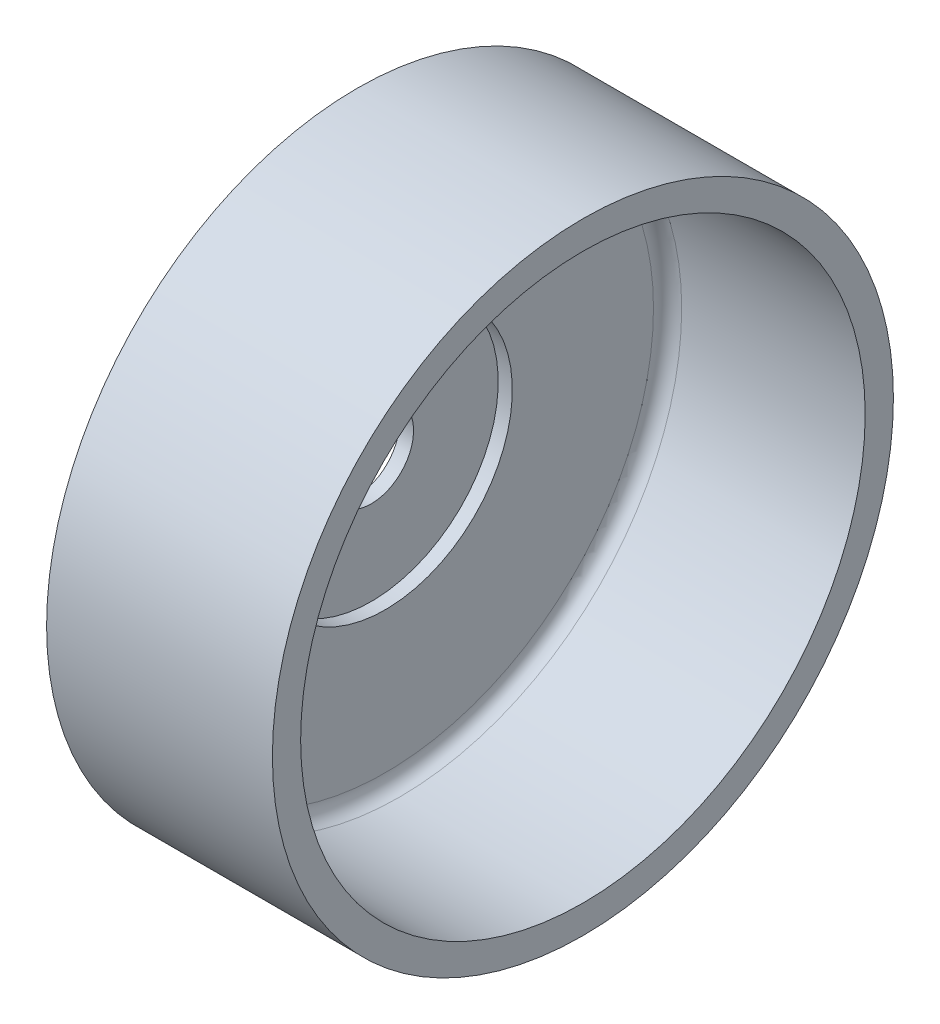
SolidWorks part; units mm, degrees
ref_plane "Front Plane" through (0, 0, 0) normal (0, 0, 1) x (1, 0, 0)
ref_plane "Top Plane" through (0, 0, 0) normal (0, 1, 0) x (1, 0, 0)
ref_plane "Right Plane" through (0, 0, 0) normal (1, 0, 0) x (0, 0, -1)
sketch "Sketch1" plane through (0, 0, 0) normal (0, 1, 0) x (1, 0, 0)
  line L0 (0, 4.7625) -> (0, 34.925)
  line L1 (0, 34.925) -> (25.4, 34.925)
  line L2 (25.4, 34.925) -> (25.4, 31.75)
  line L3 (25.4, 31.75) -> (4.7625, 31.75)
  line L4 (3.175, 30.1625) -> (3.175, 14.2875)
  line L5 (3.175, 14.2875) -> (1.5875, 14.2875)
  line L6 (1.5875, 14.2875) -> (1.5875, 4.7625)
  line L8 (1.5875, 0) -> (24.5079, 0) construction
  line L9 (0, 4.7625) -> (1.5875, 4.7625)
  arc A0 (3.175, 30.1625) -> (4.7625, 31.75) centre (4.7625, 30.1625) cw
  point P2 (0, 0)
  point P6 (0, 0)
  dimension "D8" = 1.5875
  dimension "D2" = 63.5
  dimension "D3" = 69.85
  dimension "D4" = 3.175
  dimension "D5" = 1.5875
  dimension "D6" = 9.525
  dimension "D7" = 28.575
  dimension "D12" = 22.225
revolve "Revolve1" add sketch "Sketch1" angle 360 about L8
